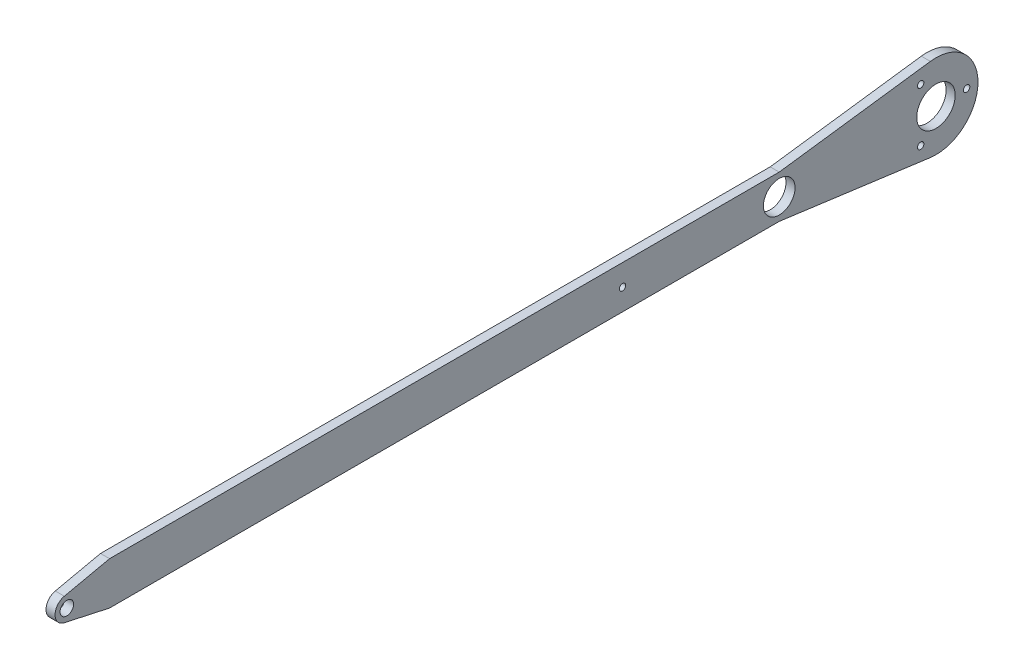
SolidWorks part; units mm, degrees
ref_plane "Front Plane" through (0, 0, 0) normal (0, 0, 1) x (1, 0, 0)
ref_plane "Top Plane" through (0, 0, 0) normal (0, 1, 0) x (1, 0, 0)
ref_plane "Right Plane" through (0, 0, 0) normal (1, 0, 0) x (0, 0, -1)
sketch "Sketch1" plane through (0, 0, 0) normal (1, 0, 0) x (0, 0, -1)
  line L0 (-470, 15) -> (-501.7607, 8.0727)
  line L1 (-470, 15) -> (0, 15)
  line L2 (-470, 15) -> (-470, -15) construction
  line L3 (-470, -15) -> (0, -15)
  line L4 (0, 15) -> (0, 11.1125) construction
  line L5 (-470, -15) -> (-501.7607, -8.0727)
  line L6 (0, 11.1125) -> (0, -11.1125) construction
  line L7 (0, -11.1125) -> (0, -15) construction
  line L8 (0, 15) -> (106.0756, 29.2378)
  line L9 (0, -15) -> (106.0756, -29.2378)
  circle A0 centre (110, 0) radius 13.5
  circle A1 centre (0, 0) radius 11.1125
  circle A2 centre (-500, 0) radius 4.7625
  arc A3 (106.0756, -29.2378) -> (106.0756, 29.2378) centre (110, 0) ccw
  arc A4 (-501.7607, 8.0727) -> (-501.7607, -8.0727) centre (-500, 0) ccw
  arc A5 (-501.7607, -8.0727) -> (-501.7607, 8.0727) centre (-500, 0) ccw construction
  arc A6 (106.0756, 29.2378) -> (106.0756, -29.2378) centre (110, 0) ccw construction
  point P13 (-470, 0)
  dimension "D3" = 22.225
  dimension "D4" = 9.525
  dimension "D5" = 27
  dimension "D6" = 59
  dimension "D7" = 3.5
  dimension "D1" = 500
  dimension "D2" = 110
  dimension "D8" = 30
  dimension "D9" = 30
extrude "Boss-Extrude1" add sketch "Sketch1" along normal mid plane 6.35
hole_wizard "M4 Clearance Hole1" positions "Sketch2" profile "Sketch3" hole size "M4" standard "ANSI Metric" end condition through all
sketch "Sketch2" plane through (3.175, 0, 0) normal (1, 0, 0) x (0, 0, -1)
  line L0 (110, 0) -> (131.5, 0) construction
  line L1 (110, 0) -> (99.25, -18.6195) construction
  line L2 (110, 0) -> (99.25, 18.6195) construction
  point P2 (131.5, 0)
  point P12 (99.25, -18.6195)
  point P13 (99.25, 18.6195)
  point P14 (-110, 0)
  point P17 (0, 0)
  dimension "D1" = 21.5
  dimension "D3" = 110
  dimension "D2" = 3
sketch "Sketch3" plane through (3.175, 0, 110) normal (0, 1, 0) x (0, 0, -1)
  line L0 (0, 0) -> (0, 6.35)
  line L1 (0, 6.35) -> (2.25, 6.35)
  line L2 (2.25, 6.35) -> (2.25, 0)
  line L5 (2.25, 0) -> (0, 0)
  line L11 (0, -6.35) -> (0, 107.95) construction
  dimension "Thru Hole Dia." = 4.5
  dimension "Thru Hole Depth" = 6.35
